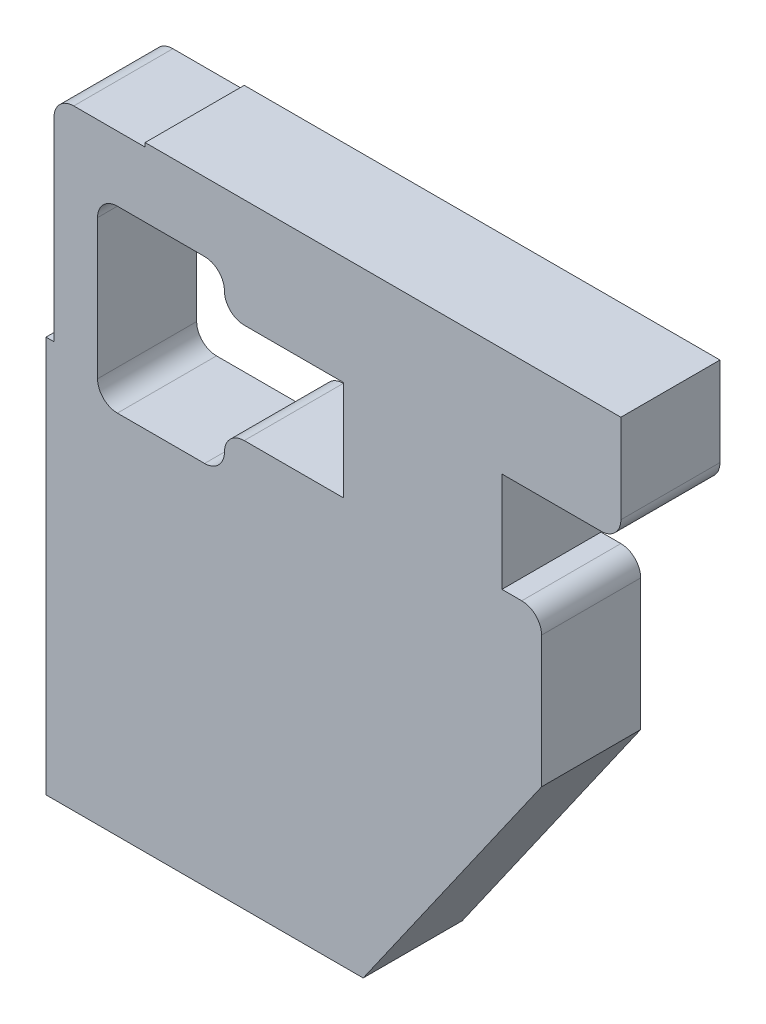
SolidWorks part; units mm, degrees
material "PBT General Purpose"
ref_plane "Front Plane" through (0, 0, 0) normal (0, 0, 1) x (1, 0, 0)
ref_plane "Top Plane" through (0, 0, 0) normal (0, 1, 0) x (1, 0, 0)
ref_plane "Right Plane" through (0, 0, 0) normal (1, 0, 0) x (0, 0, -1)
sketch "frame_outline" plane through (0, 0, 0) normal (0, 0, 1) x (1, 0, 0)
  line L0 (0, 0) -> (0, -0.6) construction
  line L1 (0, 0) -> (0.3, 0) construction
  line L2 (0, -0.6) -> (0.05, -0.6) construction
  line L3 (0.3, 0) -> (0.3, -0.05) construction
  line L8 (0.3, -0.05) -> (1.5, -0.05)
  line L19 (0.3, -0.05) -> (0.3, -0.06)
  line L20 (0.3, -0.06) -> (0.07, -0.06)
  line L21 (0.07, -0.06) -> (0.07, -0.6)
  line L62 (0.05, -0.6) -> (0.07, -0.6)
  line L63 (0.05, -0.6) -> (0.05, -1.6)
  line L64 (0.05, -1.6) -> (0.85, -1.6)
  line L65 (0.85, -1.6) -> (1.3, -0.9573)
  line L66 (1.3, -0.9573) -> (1.3, -0.576)
  line L67 (1.3, -0.576) -> (1.2, -0.576)
  line L68 (1.2, -0.576) -> (1.2, -0.324)
  line L69 (1.2, -0.324) -> (1.5, -0.324)
  line L70 (1.5, -0.324) -> (1.5, -0.05)
  line L71 (0, -0.45) -> (1.8135, -0.45) construction
  line L72 (0.5, -0.324) -> (0.8, -0.324)
  line L73 (0.8, -0.324) -> (0.8, -0.576)
  line L74 (0.8, -0.576) -> (0.5, -0.576)
  line L75 (0.5, -0.576) -> (0.5, -0.676)
  line L76 (0.5, -0.676) -> (0.18, -0.676)
  line L77 (0.18, -0.676) -> (0.18, -0.224)
  line L78 (0.18, -0.224) -> (0.5, -0.224)
  line L79 (0.5, -0.224) -> (0.5, -0.324)
  line L80 (1.2, -0.05) -> (1.2, -1.1001) construction
  point P22 (1.2, -0.45)
  dimension "D2" = 0.3
  dimension "D6" = 1.2
  dimension "D4" = 0.05
  dimension "D1" = 0.05
  dimension "D3" = 0.6
  dimension "D5" = 0.02
  dimension "D7" = 0.01
  dimension "D8" = 1
  dimension "D9" = 0.45
  dimension "D10" = 0.252
  dimension "D11" = 0.1
  dimension "D12" = 0.32
  dimension "D13" = 0.3
  dimension "D14" = 0.1
  dimension "D15" = 0.4
  dimension "D16" = 0.85
  dimension "D17" = 55
  dimension "D18" = 0.3
extrude "Boss-Extrude1" add sketch "frame_outline" along normal mid plane 0.25
fillet "Fillet1" radius 0.05 9 edges at (1.3, -0.576, 0) (1.5, -0.324, 0) (0.5, -0.324, 0) (0.5, -0.576, 0) (0.5, -0.676, 0) (0.18, -0.676, 0) (0.5, -0.224, 0) (0.18, -0.224, 0) (0.07, -0.06, 0)
equation "\"t\"= 0.25'thickness of the sheets"
equation "\"t_cf\" = 0.115'thickness of single carbon fiber layer"
equation "\"t_kapton\" = 0.025'thickness of single Kapton flex layer"
equation "\"t_fr4\" = 0.1'thickness of FR4 with copper layer"
equation "\"joint_flex\"= 0.1'Width of flextures gap"
equation "\"joint_flex_eff\"= 0.02'Width of flecture after castelation"
equation "\"joint_fold\"= 0.2'Width of folding joints for 90deg fold"
equation "\"gap_tolerance\"= 0.002'Width to have interfecence fit between carbon fiber inserts"
equation "\"assemble_angle\"= 90'Angle of assembly parts"
equation "\"D1@Boss-Extrude1\"=\"t\""
equation "\"link_lift\"= 0.5'Actuation linkage amplification for the lift motion"
equation "\"link_swing\"= 0.45'Actuation linkage amplification for the swing motion"
equation "\"D9@frame_outline\"=\"link_swing\""
equation "\"D4@frame_outline\"=\"joint_flex\"/2"
equation "\"D1@frame_outline\"=\"joint_flex\"/2"
equation "\"D10@frame_outline\"=\"t\"+\"gap_tolerance\""
